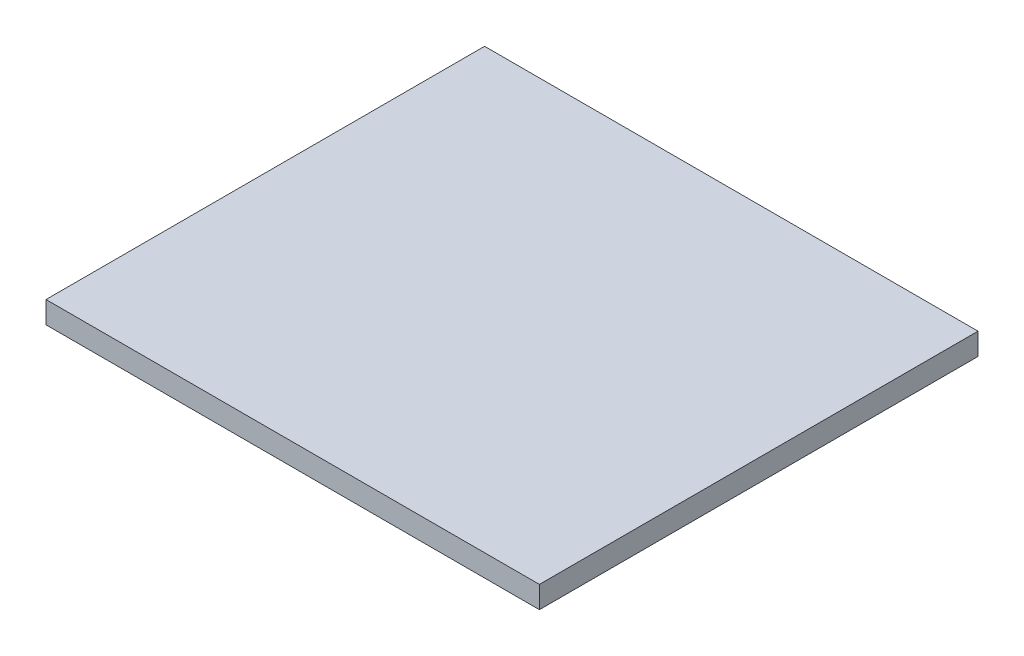
SolidWorks part; units mm, degrees
ref_plane "Alzado" through (0, 0, 0) normal (0, 0, 1) x (1, 0, 0)
ref_plane "Planta" through (0, 0, 0) normal (0, 1, 0) x (1, 0, 0)
ref_plane "Vista lateral" through (0, 0, 0) normal (1, 0, 0) x (0, 0, -1)
sketch "Croquis1" plane through (0, 0, 0) normal (0, 1, 0) x (1, 0, 0)
  line L1 (0, 0) -> (90, 0)
  line L2 (0, 0) -> (0, -80)
  line L3 (0, -80) -> (90, -80)
  line L4 (90, 0) -> (90, -80)
  dimension "D1" = 80
  dimension "D2" = 90
extrude "Saliente-Extruir1" add sketch "Croquis1" along normal blind 4
